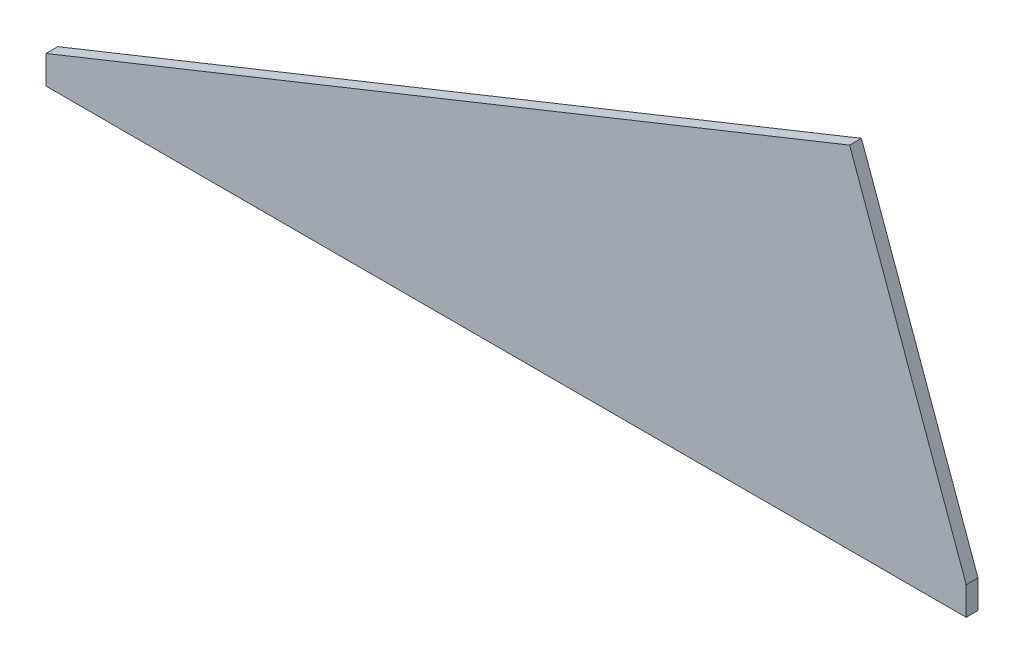
SolidWorks part; units mm, degrees
ref_plane "Front Plane" through (0, 0, 0) normal (0, 0, 1) x (1, 0, 0)
ref_plane "Top Plane" through (0, 0, 0) normal (0, 1, 0) x (1, 0, 0)
ref_plane "Right Plane" through (0, 0, 0) normal (1, 0, 0) x (0, 0, -1)
sketch "Sketch2" plane through (0, 0, 0) normal (0, 0, 1) x (1, 0, 0)
  line L0 (0, 2.255) -> (371, 2.255)
  line L1 (371, 2.255) -> (371, 13.655)
  line L2 (371, 13.655) -> (324, 143.655)
  line L3 (324, 143.655) -> (0, 13.655)
  line L4 (0, 13.655) -> (0, 2.255)
  dimension "D1" = 371
  dimension "D2" = 11.4
  dimension "D3" = 11.4
  dimension "D4" = 130
  dimension "D5" = 324
extrude "Boss-Extrude1" add sketch "Sketch2" along normal blind 4.76
